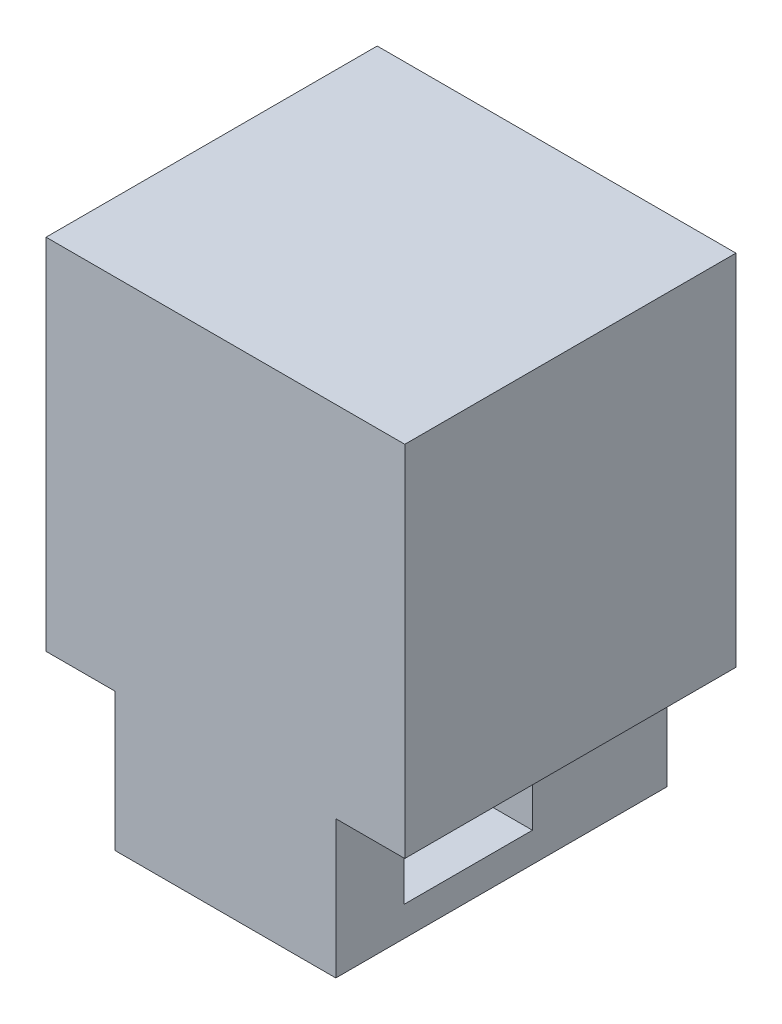
SolidWorks part; units mm, degrees
ref_plane "Front Plane" through (0, 0, 0) normal (0, 0, 1) x (1, 0, 0)
ref_plane "Top Plane" through (0, 0, 0) normal (0, 1, 0) x (1, 0, 0)
ref_plane "Right Plane" through (0, 0, 0) normal (1, 0, 0) x (0, 0, -1)
sketch "Sketch3" plane through (0, 0, 0) normal (0, 0, 1) x (1, 0, 0)
  line L1 (-65, -65) -> (65, -65)
  line L2 (-65, -65) -> (-65, 65)
  line L3 (-65, 65) -> (65, 65)
  line L4 (65, -65) -> (65, 65)
  line L5 (-65, -65) -> (65, 65) construction
  line L6 (-65, 65) -> (65, -65) construction
  point P0 (0, 0)
  dimension "D1" = 130
  dimension "D2" = 130
extrude "Boss-Extrude1" add sketch "Sketch3" against normal blind 120
sketch "Sketch4" plane through (0, 0, 0) normal (0, 0, 1) x (1, 0, 0)
  line L0 (0, -65) -> (0, -118.7219)
  line L1 (-65, -65) -> (65, -65)
  line L5 (0, 0) -> (0, -115)
  line L6 (0, -65) -> (-40, -65)
  line L7 (0, -65) -> (0, -115)
  line L8 (40, -115) -> (-40, -115)
  line L9 (-40, -65) -> (-40, -115)
  line L10 (40, -65) -> (40, -115)
  line M7 (-65, -65) -> (65, -65)
  dimension "D1" = 40
  dimension "D2" = 50
extrude "Boss-Extrude2" add sketch "Sketch4" against normal blind 120 contours L1 L9 L8 L0 | L10 L0 L8 M7 region at (20, -90, 0) region at (-20, -90, 0)
sketch "Sketch6" plane through (40, 0, 0) normal (1, 0, 0) x (0, 0, -1)
  line L0 (0, -65) -> (0, -115) construction
  line L1 (24.75, -75.75) -> (69.25, -75.75)
  line L2 (24.75, -75.75) -> (24.75, -104.25)
  line L11 (71.25, -75.75) -> (69.25, -75.75)
  line L13 (71.25, -75.75) -> (24.75, -75.75)
  line L14 (71.25, -75.75) -> (71.25, -104.25)
  line L15 (71.25, -104.25) -> (24.75, -104.25)
  line L16 (24.75, -75.75) -> (24.75, -104.25)
  line L17 (120, -65) -> (0, -65) construction
  line L18 (120, -65) -> (120, -115) construction
  circle A1 centre (60, -90) radius 10.25
  dimension "D3" = 11.25
  dimension "D4" = 48.75
  dimension "D5" = 14.25
  dimension "D6" = 20.5
  dimension "D1" = 24.75
  dimension "D2" = 10.75
extrude "Cut-Extrude3" cut sketch "Sketch6" against normal blind 34 contours L15 L14 L11 L1 L2 A1 | A1 region at (40, -90, -44.0201) region at (40, -90, -60)
ref_plane "Plane1" through (0, 0, 0) normal (1, 0, 0) x (0, 0, -1)
mirror "Mirror1" about plane through (0, 0, 0) normal (1, 0, 0) of "Cut-Extrude3"
